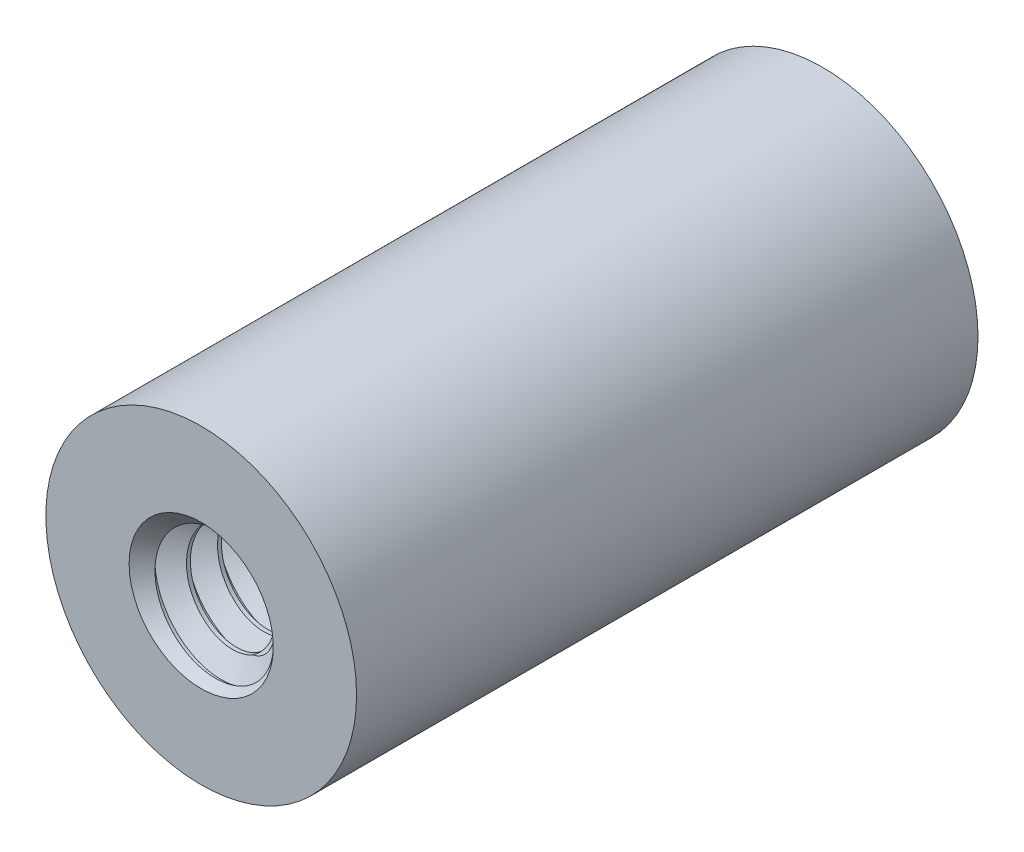
SolidWorks part; units mm, degrees
ref_plane "Front Plane" through (0, 0, 0) normal (0, 0, 1) x (1, 0, 0)
ref_plane "Top Plane" through (0, 0, 0) normal (0, 1, 0) x (1, 0, 0)
ref_plane "Right Plane" through (0, 0, 0) normal (1, 0, 0) x (0, 0, -1)
sketch "Sketch3" plane through (0, 0, 0) normal (1, 0, 0) x (0, 0, -1)
  line L0 (-6.35, 0) -> (6.35, 0) construction
  line L1 (0, 3.175) -> (0, -3.175) construction
  line L2 (-6.35, 1.4224) -> (-6.35, -1.4224) construction
  point P2 (-4.7625, 0)
  point P3 (4.7625, 0)
  dimension "Length" = 12.7
  dimension "Min Thread Length" = 11.1125
  dimension "D1" = 11.1125
  dimension "Thread Dia" = 2.8448
  dimension "OD" = 6.35
sketch "Sketch1" plane through (0, 0, 0) normal (0, 0, 1) x (1, 0, 0)
  circle A1 centre (0, 0) radius 1.4224
  circle A2 centre (0, 0) radius 3.175
extrude "Extrude1" add sketch "Sketch1" along normal up to vertex (6.35 mm away) and the other way up to vertex (6.35 mm away) up to point (0, 0, 6.35) other way up to point (0, 0, -6.35)
sketch "Sketch11" plane through (0, 0, -6.35) normal (0, 0, -1) x (-1, 0, 0)
  circle A0 centre (0, 0) radius 1.4224 construction
  circle A1 centre (0, 0) radius 1.4224
curve "Helix/Spiral1" pitch 0.635 height 13.335 radius 1.4224 centre (0, 0, -6.35) axis (0, 0, 1) start towards (0, 1, 0) parameters "Pitch"=0.635
sketch "Sketch12" plane through (0, 0, 0) normal (1, 0, 0) x (0, 0, -1)
  line L0 (6.9056, 1.4224) -> (6.35, 1.4224)
  line L1 (6.9056, 1.4224) -> (6.6675, 1.01)
  line L2 (6.6675, 1.01) -> (6.5881, 1.01)
  line L3 (6.5881, 1.01) -> (6.35, 1.4224)
  line L4 (6.6278, 1.01) -> (6.6278, 1.4224) construction
  line L5 (6.7866, 1.2162) -> (6.4691, 1.2162) construction
  dimension "D1" = 0.0794
  dimension "D2" = 0.3175
  dimension "D3" = 60
sweep "Sweep1" add profiles "Sketch12" path "Helix/Spiral1"
sketch "Sketch6" plane through (0, 0, -6.35) normal (0, 0, -1) x (-1, 0, 0)
  circle A1 centre (0, 0) radius 3.175
  circle A2 centre (0, 0) radius 3.175
  dimension "D1" = 0
extrude "Extrude2" cut sketch "Sketch6" along normal through all
sketch "Sketch7" plane through (0, 0, -6.35) normal (0, 0, -1) x (-1, 0, 0)
  circle A2 centre (0, 0) radius 1.4732
  circle A3 centre (0, 0) radius 1.4732
  dimension "D1" = 0.0508
extrude "Extrude3" cut sketch "Sketch7" against normal through all draft 43
mirror "Mirror1" about plane through (0, 0, 0) normal (0, 0, 1) of "Extrude2", "Extrude3"
sketch "Sketch9" [suppressed] plane through (0, 0, 0) normal (1, 0, 0) x (0, 0, -1)
  line L1 (-20.6375, 2.1336) -> (20.6375, 2.1336)
  line L2 (-20.6375, 2.1336) -> (-20.6375, 0)
  line L3 (-20.6375, 0) -> (20.6375, 0)
  line L4 (20.6375, 2.1336) -> (20.6375, 0)
  line L7 (-31.75, 0) -> (31.75, 0) construction
revolve "Revolve" [suppressed] add sketch "Sketch9" angle 360 about L0
sketch "Sketch10" [suppressed] plane through (0, 0, 0) normal (1, 0, 0) x (0, 0, -1)
  line L0 (31.75, 2.0828) -> (20.6375, 2.0828)
  line L1 (-31.75, 2.0828) -> (-20.6375, 2.0828)
  line L2 (20.6375, 2.0828) -> (20.6375, -2.0828)
  line L3 (-31.75, -2.1336) -> (-20.6375, -2.1336)
  line L4 (-20.6375, 2.0828) -> (-20.6375, -2.1336)
  line L5 (20.6375, -2.0828) -> (31.75, -2.0828)
equation "\"D1@Sketch3\" = \"Min Thread Length@Sketch3\""
equation "\"D3@Helix/Spiral1\" = \"Length@Sketch3\"+\"Pitch@Helix/Spiral1\""
equation "\"D1@Sketch12\" = \"Pitch@Helix/Spiral1\"*.125"
equation "\"D2@Sketch12\" = \"Pitch@Helix/Spiral1\"*.5"
